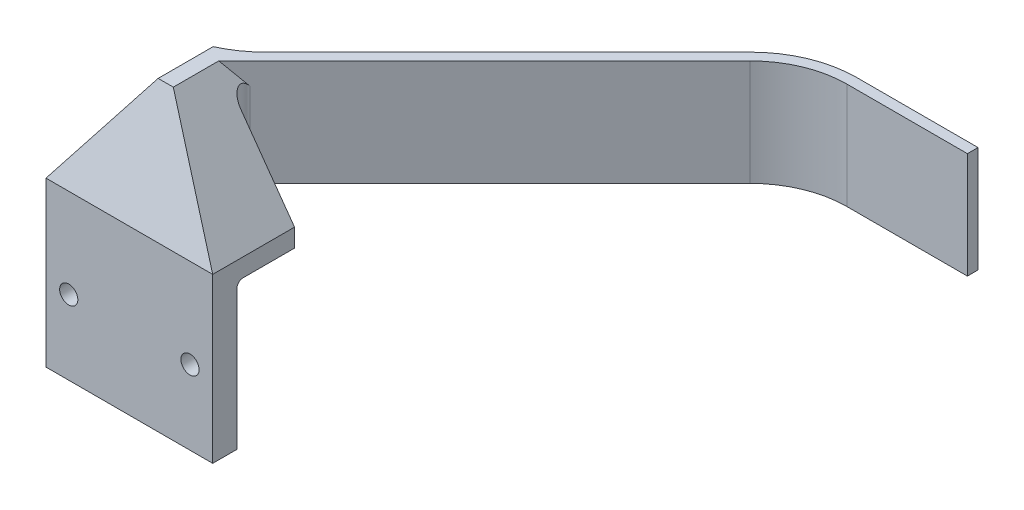
SolidWorks part; units mm, degrees
ref_plane "Front Plane" through (0, 0, 0) normal (0, 0, 1) x (1, 0, 0)
ref_plane "Top Plane" through (0, 0, 0) normal (0, 1, 0) x (1, 0, 0)
ref_plane "Right Plane" through (0, 0, 0) normal (1, 0, 0) x (0, 0, -1)
sketch "Sketch1" plane through (0, 0, 0) normal (0, 0, 1) x (1, 0, 0)
  line L0 (0, 0) -> (0, 28.3636) construction
  line L1 (-27.5, -24) -> (27.5, -24)
  line L2 (-27.5, -24) -> (-27.5, 24)
  line L3 (-27.5, 24) -> (27.5, 24)
  line L4 (27.5, -24) -> (27.5, 24)
  line L5 (-27.5, -24) -> (27.5, 24) construction
  line L6 (-27.5, 24) -> (27.5, -24) construction
  circle A0 centre (20, 0.5) radius 3
  circle A1 centre (-20, 0.5) radius 3
  point P0 (0, 0)
  dimension "D2" = 40
  dimension "D5" = 6
  dimension "D1" = 48
  dimension "D3" = 23.5
  dimension "D4" = 55
extrude "Boss-Extrude1" add sketch "Sketch1" along normal blind 8
sketch "Sketch2" plane through (0, 24, 0) normal (0, 1, 0) x (1, 0, 0)
  line L0 (27.5, 0) -> (-27.5, 0) construction
  line L1 (-27.5, -8) -> (27.5, -8)
  line L2 (-27.5, -8) -> (-27.5, 19)
  line L3 (-27.5, 19) -> (27.5, 19)
  line L4 (27.5, -8) -> (27.5, 19)
  line L5 (27.5, -8) -> (27.5, 0) construction
  dimension "D1" = 19
extrude "Boss-Extrude2" add sketch "Sketch2" along normal blind 6
sketch "Sketch3" plane through (0, 0, 0) normal (1, 0, 0) x (0, 0, -1)
  line L0 (4, 30) -> (4, 65)
  line L1 (-8, 30) -> (19, 30) construction
  line L2 (4, 65) -> (19, 65)
  line L3 (19, 65) -> (19, 30)
  line L4 (19, 30) -> (4, 30)
  line L5 (0, -24) -> (0, 24) construction
  line L6 (-8, -24) -> (-8, 30) construction
  dimension "D1" = 19
  dimension "D2" = 35
  dimension "D3" = 12
extrude "Boss-Extrude3" add sketch "Sketch3" along normal mid plane 5
fillet "Fillet1" radius 2 1 edges at (0, 24, 0)
sketch "Sketch4" plane through (0, 0, 0) normal (1, 0, 0) x (0, 0, -1)
  line L0 (4, 65) -> (-8, 30)
rib "Rib1" sketch "Sketch4" sketch "Sketch4" thickness 5 extrusion direction parallel to sketch draft on no parameters "D1"=5
sketch "Sketch5" plane through (0, 0, -19) normal (0, 0, -1) x (-1, 0, 0)
  line L0 (-27.5, 30) -> (-2.5, 65)
  line L1 (-2.5, 65) -> (-2.5, 30)
  line L2 (-2.5, 30) -> (-27.5, 30)
extrude "Boss-Extrude5" add sketch "Sketch5" against normal up to surface (27 mm away) up to face at (0, 47.5, 2)
mirror "Mirror1" about plane through (0, 0, 0) normal (1, 0, 0) of "Boss-Extrude5"
sketch "Sketch7" plane through (0, 65, 0) normal (0, 1, 0) x (1, 0, 0)
  line L0 (0, 0) -> (0, 170.9831) construction
  line L1 (-158.8009, 127) -> (203.9133, 127) construction
  line L2 (0, 19) -> (98.75, 117.75) construction
  line L3 (-27.5, 0) -> (27.5, 0) construction
  line L4 (0, 19) -> (-96.25, 115.25) construction
  line L5 (2.5, 19) -> (-2.5, 19) construction
  line L12 (2.5, 19) -> (-2.5, 19)
  line L14 (98.75, 117.75) -> (166.3607, 117.75) construction
  line L15 (-2.5, 19) -> (98, 119.5)
  line L16 (98, 119.5) -> (152.5, 119.5)
  line L17 (152.5, 119.5) -> (152.5, 116)
  line L18 (152.5, 116) -> (99.5, 116)
  line L19 (99.5, 116) -> (2.5, 19)
  line L20 (-27.5, 19) -> (-27.5, -8) construction
  dimension "D1" = 127
  dimension "D2" = 45
  dimension "D6" = 45
  dimension "D7" = 7.5
  dimension "D8" = 3.5
  dimension "D9" = 180
ref_axis "Axis1" through (-27.5, -24, 0) along (1, 0, 0)
extrude "Boss-Extrude6" add sketch "Sketch7" against normal blind 35
fillet "Fillet3" radius 35 1 edges at (98, 47.5, -119.5)
fillet "Fillet4" radius 32 1 edges at (99.5, 47.5, -116)
fillet "Fillet5" radius 35 1 edges at (-2.5, 47.5, -19)
fillet "Fillet6" radius 3 1 edges at (2.5, 47.5, -19)
